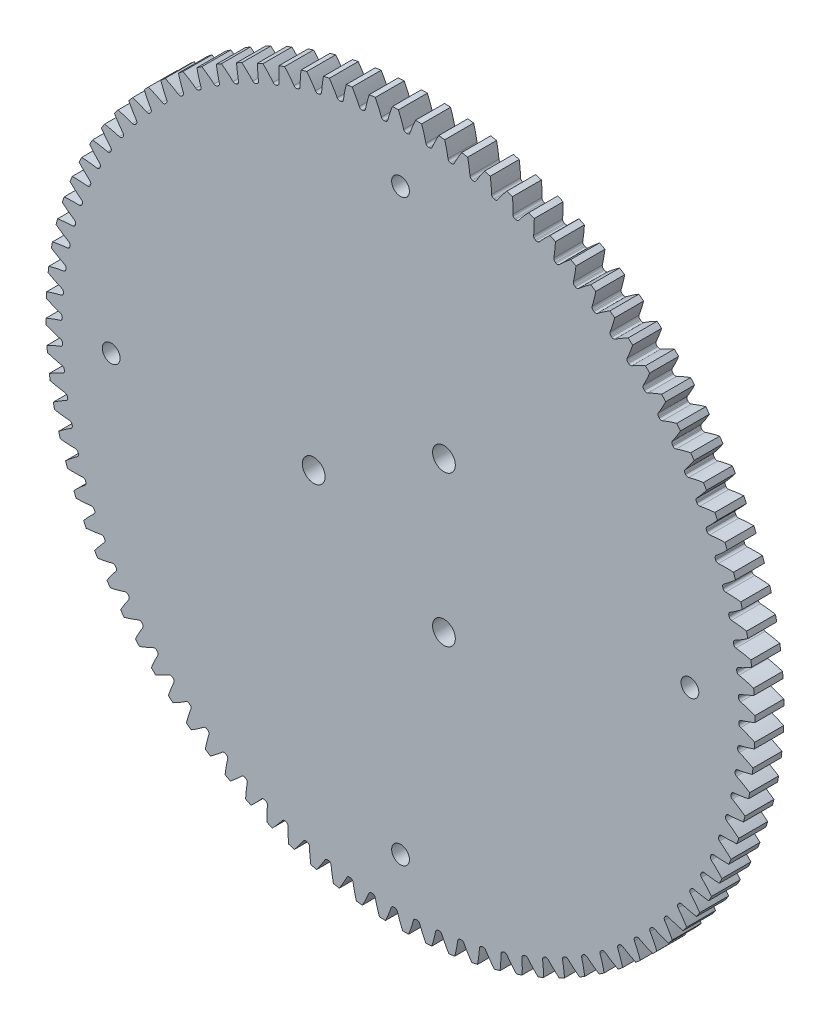
SolidWorks part; units mm, degrees
ref_plane "Front" through (0, 0, 0) normal (0, 0, 1) x (1, 0, 0)
ref_plane "Top" through (0, 0, 0) normal (0, 1, 0) x (1, 0, 0)
ref_plane "Right" through (0, 0, 0) normal (1, 0, 0) x (0, 0, -1)
sketch "Sketch3" plane through (0, 0, 0) normal (0, 0, 1) x (1, 0, 0)
  circle A0 centre (0, 0) radius 77.7875
  dimension "od" = 155.575
extrude "gearBody" add sketch "Sketch3" along normal blind 6.35
sketch "Sketch2" plane through (0, 0, 0) normal (0, 0, 1) x (1, 0, 0)
  line L0 (0, 0) -> (66.154, 27.4019) construction
  line L1 (89.9379, -14.1817) -> (0, 0) construction
  line L2 (0, 0) -> (36.3143, 0) construction
  line L3 (76.1998, -0.172) -> (76.1546, -2.6294) construction
  line L5 (76.1772, -1.4007) -> (0, 0) construction
  line L7 (0, 0) -> (71.6046, 0) construction
  arc A0 (71.5902, -1.4371) -> (71.5946, -1.1957) centre (0, 0) ccw construction
  arc A1 (77.7861, 0.4588) -> (77.7167, -3.3181) centre (0, 0) ccw construction
  arc A2 (76.1998, -0.172) -> (76.1546, -2.6294) centre (0, 0) ccw construction
  arc A3 (74.2296, -1.47) -> (74.2335, -1.2598) centre (0, 0) ccw
  arc A4 (89.9379, -14.1817) -> (74.6441, -2.0632) centre (65.1019, -29.8153) ccw
  arc A5 (89.9379, -14.1817) -> (90.3984, 10.8657) centre (0, 0) ccw
  arc A6 (90.3984, 10.8657) -> (74.6695, -0.6823) centre (66.154, 27.4019) cw
  arc A7 (74.2335, -1.2598) -> (74.6695, -0.6823) centre (74.8478, -1.2702) cw
  arc A8 (74.6441, -2.0632) -> (74.2296, -1.47) centre (74.8439, -1.4822) cw
  point P6 (90.3984, 10.8657)
  point P22 (89.9379, -14.1817)
  dimension "baseDia" = 143.2092
  dimension "od" = 155.575
  dimension "pd" = 152.4
  dimension "rd" = 148.4884
  dimension "rFillet" = 0.6144
  dimension "pointX" = 90.3984
  dimension "pointY" = 10.8657
  dimension "CTT" = 2.4574
  dimension "flankCenterAngle" = 22.5
extrude "toothCut" cut sketch "Sketch2" along normal through all
pattern_circular "CirPattern1" count 96 over 360 about axis through (0, 0, 6.35) along (0, 0, -1) of "toothCut"
sketch "hub1Dia" plane through (0, 0, 0) normal (0, 0, -1) x (-1, 0, 0)
  circle A0 centre (0, 0) radius 12.7
  dimension "hub1Dia" = 25.4
sketch "hub2Dia" plane through (0, 0, 6.35) normal (0, 0, 1) x (1, 0, 0)
  circle A0 centre (0, 0) radius 12.7
  dimension "hub2dia" = 25.4
sketch "boreDia" plane through (0, 0, 0) normal (0, 0, 1) x (1, 0, 0)
  circle A0 centre (0, 0) radius 7.9375
  dimension "boreDia" = 15.875
sketch "Sketch4" plane through (0, 0, 0) normal (0, 0, -1) x (-1, 0, 0)
  circle A0 centre (19.05, 0) radius 2.5
  circle A1 centre (-9.525, -16.4978) radius 2.5
  circle A2 centre (-9.525, 16.4978) radius 2.5
  point P10 (0, 0)
  dimension "D2" = 5
  dimension "D1" = 19.05
  dimension "D3" = 3
extrude "Cut-Extrude1" cut sketch "Sketch4" against normal through all
sketch "Sketch5" plane through (0, 0, 0) normal (0, 0, -1) x (-1, 0, 0)
  circle A0 centre (63.5, 0) radius 1.95
  circle A1 centre (0, -63.5) radius 1.95
  circle A2 centre (-63.5, 0) radius 1.95
  circle A3 centre (0, 63.5) radius 1.95
  point P12 (0, 0)
  dimension "D1" = 3.9
  dimension "D2" = 63.5
  dimension "D3" = 4
extrude "Cut-Extrude2" cut sketch "Sketch5" against normal through all
equation "\"D2@Sketch4\"=5mm"
equation "\"D1@Sketch5\"=3.9mm"
